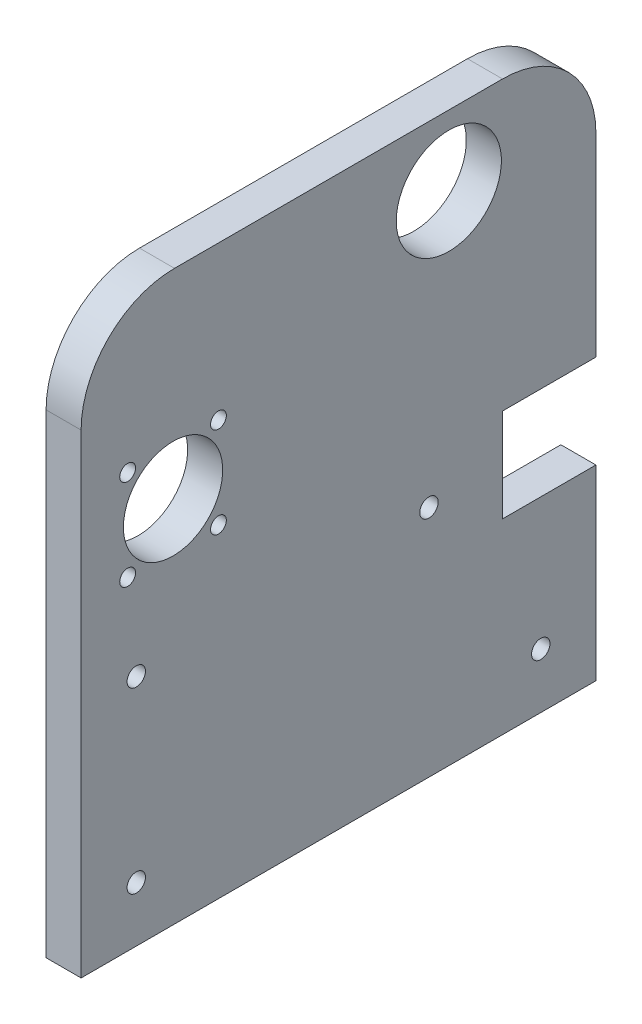
SolidWorks part; units mm, degrees
ref_plane "Front Plane" through (0, 0, 0) normal (0, 0, 1) x (1, 0, 0)
ref_plane "Top Plane" through (0, 0, 0) normal (0, 1, 0) x (1, 0, 0)
ref_plane "Right Plane" through (0, 0, 0) normal (1, 0, 0) x (0, 0, -1)
sketch "Sketch1" plane through (0, 0, 0) normal (0, 1, 0) x (1, 0, 0)
  line L1 (-4.7625, 70) -> (4.7625, 70)
  line L2 (-4.7625, 70) -> (-4.7625, -70)
  line L3 (-4.7625, -70) -> (4.7625, -70)
  line L4 (4.7625, 70) -> (4.7625, -70)
  line L5 (-4.7625, 70) -> (4.7625, -70) construction
  line L6 (-4.7625, -70) -> (4.7625, 70) construction
  point P0 (0, 0)
  dimension "D1" = 140
  dimension "D2" = 9.525
extrude "Boss-Extrude1" add sketch "Sketch1" along normal mid plane 154.4436
fillet "Fillet1" radius 25.4 2 edges at (0, 77.2218, 70) (0, 77.2218, -70)
sketch "Sketch5" plane through (-4.7625, 0, 0) normal (-1, 0, 0) x (0, 0, 1)
  line L1 (-70, 51.8218) -> (-70, -77.2218) construction
  line L2 (-70, -0.9964) -> (-44.6, -0.9964)
  line L3 (-70, -0.9964) -> (-70, -26.3964)
  line L4 (-70, -26.3964) -> (-44.6, -26.3964)
  line L5 (-70, -77.2218) -> (70, -77.2218) construction
  line L6 (-44.6, -0.9964) -> (-44.6, -26.3964)
  dimension "D3" = 25.4
  dimension "D1" = 50.8254
  dimension "D2" = 25.4
sketch "Sketch3" plane through (-4.7625, 0, 0) normal (-1, 0, 0) x (0, 0, 1)
  line L0 (45, 23.1718) -> (61.409, 39.5809) construction
  line L2 (-70, 51.8218) -> (-70, -77.2218) construction
  line L3 (-45.4613, 23.1718) -> (44.137, 23.1718) construction
  line L6 (45, 46.9613) -> (45, -2.4047) construction
  line L7 (-44.6, 77.2218) -> (44.6, 77.2218) construction
  line L8 (70, 51.8218) -> (70, -77.2218) construction
  circle A0 centre (-30, 58.1718) radius 14.29
  circle A1 centre (32.6521, 35.5197) radius 2.15
  circle A2 centre (57.3479, 35.5197) radius 2.15
  circle A3 centre (32.6521, 10.824) radius 2.15
  circle A4 centre (57.3479, 10.824) radius 2.15
  circle A5 centre (45, 23.1718) radius 13.5
  circle A6 centre (45, 23.1718) radius 17.4625 construction
  dimension "D1" = 28.58
  dimension "D2" = 19.05
  dimension "D3" = 45
  dimension "D4" = 12.3479
  dimension "D7" = 27
  dimension "D8" = 4.3
  dimension "D10" = 35
  dimension "D11" = 25
  dimension "Bolt circle" = 34.925
  dimension "D9" = 40
extrude "Cut-Extrude2" cut sketch "Sketch3" against normal blind 28.575
extrude "Cut-Extrude4" cut sketch "Sketch5" against normal through all
ref_axis "Axis1" through (4.7625, 58.1718, -30) along (-1, 0, 0)
hole_wizard "M6 Tapped Hole1" positions "Sketch7" profile "Sketch6" tap size "M6" standard "DIN"
sketch "Sketch7" plane through (0, 0, -44.6) normal (0, 0, -1) x (-1, 0, 0)
  line L1 (-4.7625, -26.3964) -> (4.7625, -26.3964) construction
  point P0 (0, -13.6964)
  dimension "D1" = 12.7
sketch "Sketch6" plane through (0, -13.6964, -44.6) normal (1, 0, 0) x (0, 1, 0)
  line L0 (0, 0) -> (0, 11.5022)
  line L1 (0, 11.5022) -> (2.5, 10)
  line L2 (2.5, 10) -> (2.5, 0)
  line L5 (2.5, 0) -> (0, 0)
  line L10 (0, 11.5022) -> (-2.5, 10) construction
  line L11 (0, -6.35) -> (0, 107.95) construction
  dimension "Tap Drill Dia." = 5
  dimension "Tap Drill Depth" = 10
  dimension "Drill Angle" = 118
cosmetic thread "Hole Thread1" parameters "D1"=10, "D2"=6
hole_wizard "M6 Tapped Hole2" positions "Sketch9" profile "Sketch8" tap size "M6" standard "DIN" end condition through all
sketch "Sketch9" plane through (-4.7625, 0, 0) normal (-1, 0, 0) x (0, 0, 1)
  line L0 (-44.6, -26.3964) -> (-44.6, -0.9964) construction
  line L1 (-70, -26.3964) -> (-70, -77.2218) construction
  line L2 (70, 51.8218) -> (70, -77.2218) construction
  line L3 (-44.6, -0.9964) -> (-70, -0.9964) construction
  line L5 (-70, -77.2218) -> (70, -77.2218) construction
  point P0 (-24.6, -13.6964)
  point P2 (55, -13.6964)
  point P4 (-55, -62.2218)
  point P6 (55, -62.2218)
  dimension "D1" = 20
  dimension "D2" = 15
  dimension "D3" = 15
  dimension "D4" = 15
  dimension "D5" = 12.7
  dimension "D6" = 12.7
  dimension "D7" = 15
  dimension "D8" = 15
sketch "Sketch8" plane through (-4.7625, -13.6964, -24.6) normal (0, 1, 0) x (0, 0, 1)
  line L0 (0, 0) -> (0, 9.525)
  line L1 (0, 9.525) -> (2.5, 9.525)
  line L2 (2.5, 9.525) -> (2.5, 0)
  line L5 (2.5, 0) -> (0, 0)
  line L11 (0, -6.35) -> (0, 107.95) construction
  dimension "Thru Tap Drill Dia." = 5
  dimension "Thru Tap Drill Depth" = 9.525
cosmetic thread "Hole Thread2" parameters "D2"=6
cosmetic thread "Hole Thread3" parameters "D2"=6
cosmetic thread "Hole Thread4" parameters "D2"=6
cosmetic thread "Hole Thread5" parameters "D2"=6
